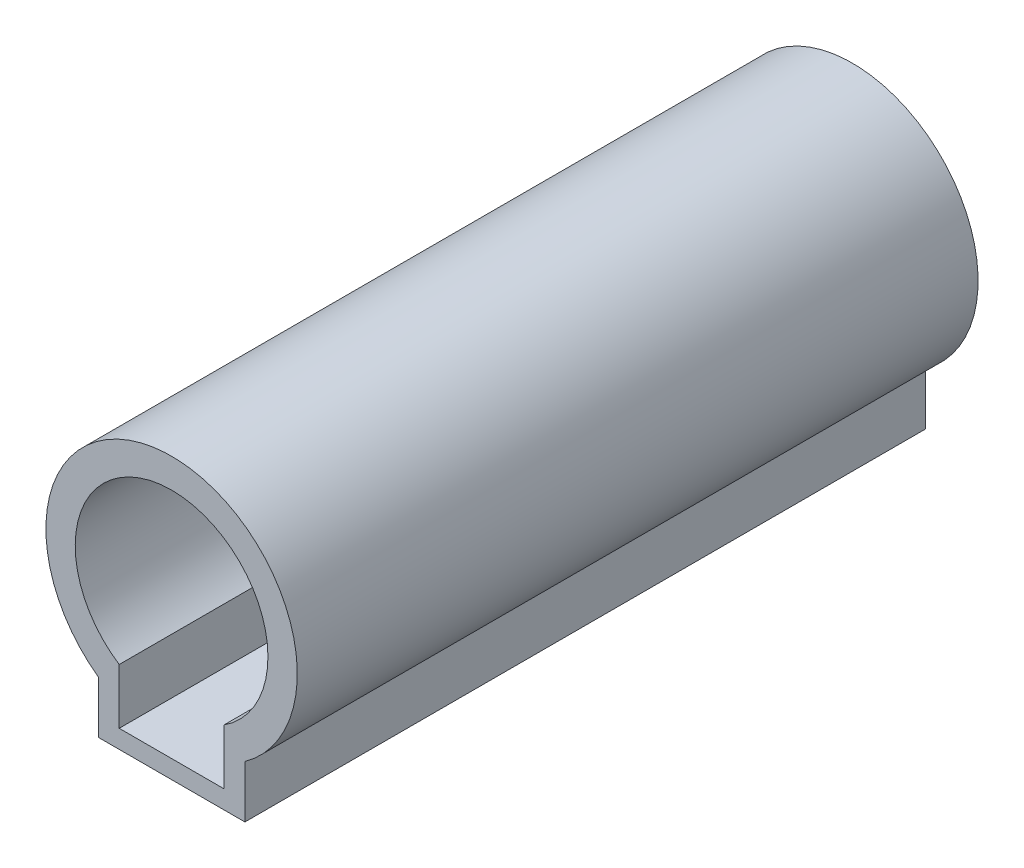
SolidWorks part; units mm, degrees
ref_plane "Front Plane" through (0, 0, 0) normal (0, 0, 1) x (1, 0, 0)
ref_plane "Top Plane" through (0, 0, 0) normal (0, 1, 0) x (1, 0, 0)
ref_plane "Right Plane" through (0, 0, 0) normal (1, 0, 0) x (0, 0, -1)
sketch "Sketch1" plane through (0, 0, 0) normal (0, 0, 1) x (1, 0, 0)
  line L0 (-7, -14.7468) -> (7, -14.7468)
  line L1 (-7, -14.7468) -> (-7, -9.7468)
  line L2 (7, -14.7468) -> (7, -9.7468)
  circle A0 centre (0, 0) radius 12
  circle A1 centre (0, 0) radius 9.2
  dimension "D1" = 24
  dimension "D2" = 18.4
  dimension "D3" = 14
  dimension "D4" = 5
extrude "Boss-Extrude1" add sketch "Sketch1" along normal blind 65 contours A0 A1 | A0 L1 L0 | A0 L0 L2 region at (0, -12.9502, 0) region at (-5.3223, 10.3751, 0)
sketch "Sketch2" plane through (0, 0, 0) normal (0, 0, 1) x (1, 0, 0)
  line L1 (5, -0.6016) -> (-5, -0.6016)
  line L2 (5, -0.6016) -> (5, -13)
  line L3 (5, -13) -> (-5, -13)
  line L4 (-5, -0.6016) -> (-5, -13)
  line L5 (5, -0.6016) -> (-5, -13) construction
  line L6 (5, -13) -> (-5, -0.6016) construction
  point P0 (0, -6.8008)
  point P5 (0, -13)
  dimension "D1" = 13
  dimension "D2" = 10
extrude "Cut-Extrude3" cut sketch "Sketch2" along normal through all
